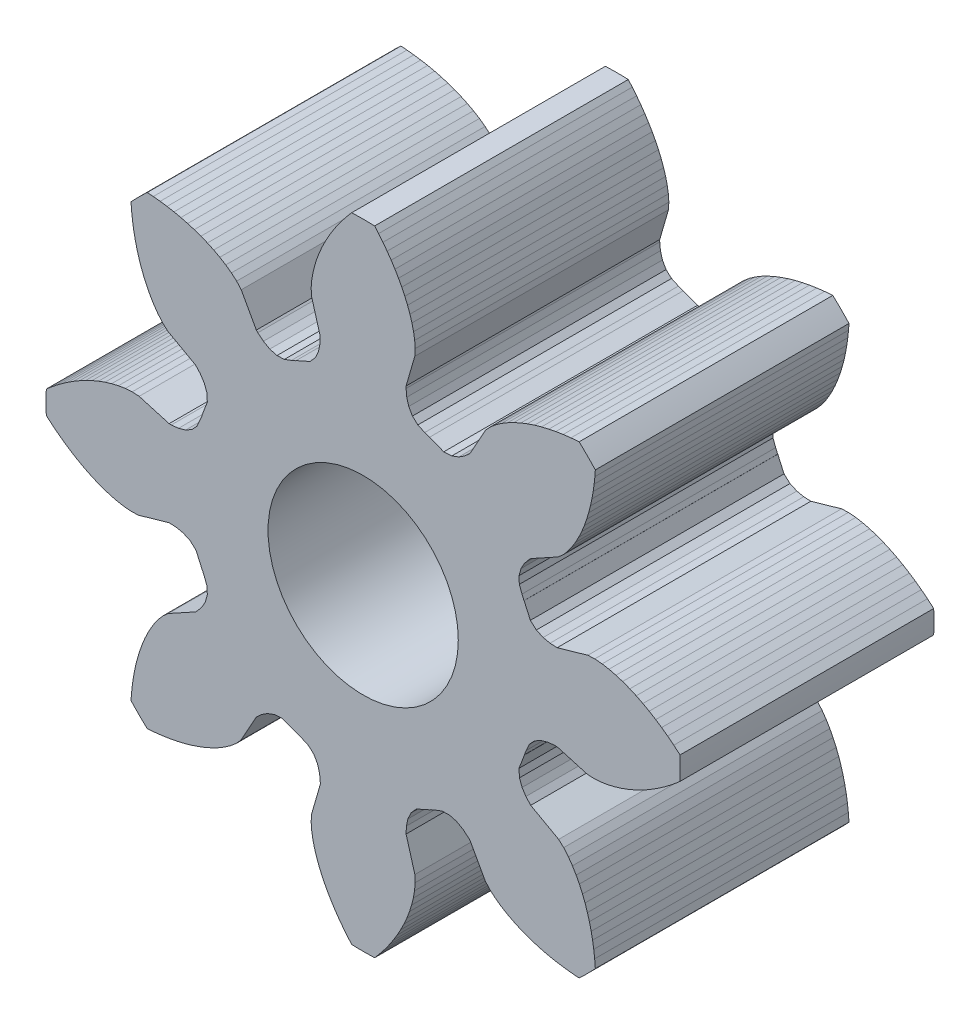
SolidWorks part; units mm, degrees
ref_plane "Front Plane" through (0, 0, 0) normal (0, 0, 1) x (1, 0, 0)
ref_plane "Top Plane" through (0, 0, 0) normal (0, 1, 0) x (1, 0, 0)
ref_plane "Right Plane" through (0, 0, 0) normal (1, 0, 0) x (0, 0, -1)
sketch "Model" plane through (0, 0, 0) normal (0, 0, 1) x (1, 0, 0)
  line L98 (2.1653, 5.052) -> (1.9418, 5.1422)
  line L99 (1.9418, 5.1422) -> (1.7243, 5.2403)
  line L100 (1.7243, 5.2403) -> (1.5535, 5.3975)
  line L101 (1.5535, 5.3975) -> (1.4379, 5.6017)
  line L102 (1.4379, 5.6017) -> (1.3749, 5.8232)
  line L103 (1.3749, 5.8232) -> (1.3531, 6.0505)
  line L104 (1.3531, 6.0505) -> (1.3533, 6.1188)
  line L105 (1.3533, 6.1188) -> (1.4203, 6.3504)
  line L106 (1.4203, 6.3504) -> (1.4872, 6.582)
  line L107 (1.4872, 6.582) -> (1.5541, 6.8136)
  line L108 (1.5541, 6.8136) -> (1.627, 7.0656)
  line L109 (1.627, 7.0656) -> (1.6406, 7.2843)
  line L110 (1.6406, 7.2843) -> (1.6247, 7.5014)
  line L111 (1.6247, 7.5014) -> (1.5893, 7.7186)
  line L112 (1.5893, 7.7186) -> (1.5382, 7.9333)
  line L113 (1.5382, 7.9333) -> (1.4749, 8.1414)
  line L114 (1.4749, 8.1414) -> (1.4, 8.3468)
  line L115 (1.4, 8.3468) -> (1.3134, 8.5512)
  line L116 (1.3134, 8.5512) -> (1.2175, 8.751)
  line L117 (1.2175, 8.751) -> (1.1147, 8.9431)
  line L118 (1.1147, 8.9431) -> (1.0027, 9.1333)
  line L119 (1.0027, 9.1333) -> (0.8826, 9.3201)
  line L120 (0.8826, 9.3201) -> (0.7557, 9.5021)
  line L121 (0.7557, 9.5021) -> (0.6232, 9.6783)
  line L122 (0.6232, 9.6783) -> (0.4866, 9.8476)
  line L123 (0.4866, 9.8476) -> (0.3614, 9.9935)
  line L128 (-0.3614, 9.9935) -> (-0.5292, 9.7961)
  line L129 (-0.5292, 9.7961) -> (-0.6811, 9.6029)
  line L130 (-0.6811, 9.6029) -> (-0.8194, 9.4126)
  line L131 (-0.8194, 9.4126) -> (-0.9445, 9.2258)
  line L132 (-0.9445, 9.2258) -> (-1.07, 9.02)
  line L133 (-1.07, 9.02) -> (-1.1806, 8.8223)
  line L134 (-1.1806, 8.8223) -> (-1.2862, 8.6102)
  line L135 (-1.2862, 8.6102) -> (-1.3751, 8.4083)
  line L136 (-1.3751, 8.4083) -> (-1.4614, 8.1811)
  line L137 (-1.4614, 8.1811) -> (-1.5275, 7.9717)
  line L138 (-1.5275, 7.9717) -> (-1.5823, 7.752)
  line L139 (-1.5823, 7.752) -> (-1.6203, 7.5357)
  line L140 (-1.6203, 7.5357) -> (-1.6402, 7.303)
  line L141 (-1.6402, 7.303) -> (-1.6306, 7.0861)
  line L142 (-1.6306, 7.0861) -> (-1.5642, 6.8544)
  line L143 (-1.5642, 6.8544) -> (-1.4978, 6.6227)
  line L144 (-1.4978, 6.6227) -> (-1.4313, 6.3909)
  line L145 (-1.4313, 6.3909) -> (-1.3649, 6.1592)
  line L146 (-1.3649, 6.1592) -> (-1.3533, 6.1188)
  line L147 (-1.3533, 6.1188) -> (-1.3641, 5.8942)
  line L148 (-1.3641, 5.8942) -> (-1.4107, 5.6774)
  line L149 (-1.4107, 5.6774) -> (-1.5086, 5.4622)
  line L150 (-1.5086, 5.4622) -> (-1.6777, 5.2728)
  line L151 (-1.6777, 5.2728) -> (-1.8978, 5.1745)
  line L152 (-1.8978, 5.1745) -> (-2.1179, 5.0761)
  line L1240 (-1.1552, 2.7687) -> (-2.1179, 5.0761)
  line L1241 (2.1653, 5.052) -> (1.1818, 2.7574)
  circle A0 centre (0, 0) radius 8 construction
  arc A1 (1.1818, 2.7574) -> (-1.1552, 2.7687) centre (0, 0) ccw
  arc A3 (0.3614, 9.9935) -> (-0.3614, 9.9935) centre (0, 0) ccw
  dimension "D1" = 16
  dimension "D2" = 6
extrude "Boss-Extrude1" add sketch "Model" along normal blind 8
ref_axis "Axis1" through (0, 0, -0.4) along (0, 0, 1)
pattern_circular "CirPattern1" count 8 over 360 about axis through (0, 0, -0.4) along (0, 0, 1) of "Boss-Extrude1"
